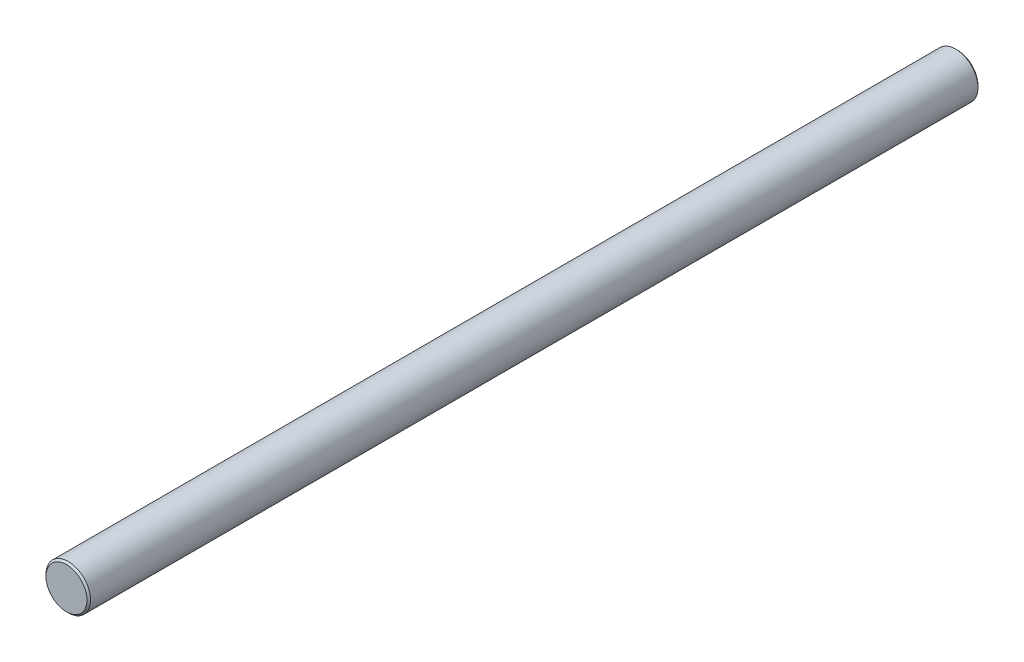
SolidWorks part; units mm, degrees
material "AISI 304"
ref_plane "Спереди" through (0, 0, 0) normal (0, 0, 1) x (1, 0, 0)
ref_plane "Сверху" through (0, 0, 0) normal (0, 1, 0) x (1, 0, 0)
ref_plane "Справа" through (0, 0, 0) normal (1, 0, 0) x (0, 0, -1)
ref_axis "ОсьX" through (-88.99, 0, 0) along (1, 0, 0)
ref_axis "ОсьZ" through (0, 55, 0) along (0, -1, 0)
ref_axis "ОсьY" through (0, 0, -88.99) along (0, 0, 1)
sketch "Эскиз1" plane through (0, 0, 0) normal (0, 0, 1) x (1, 0, 0)
  circle A0 centre (0, 0) radius 12.5
  dimension "D1" = 25
extrude "Бобышка-Вытянуть1" add sketch "Эскиз1" along normal mid plane 500
chamfer "Фаска1" distance 1 angle 45 2 edges at (12.5, 0, -250) (12.5, 0, 250)
